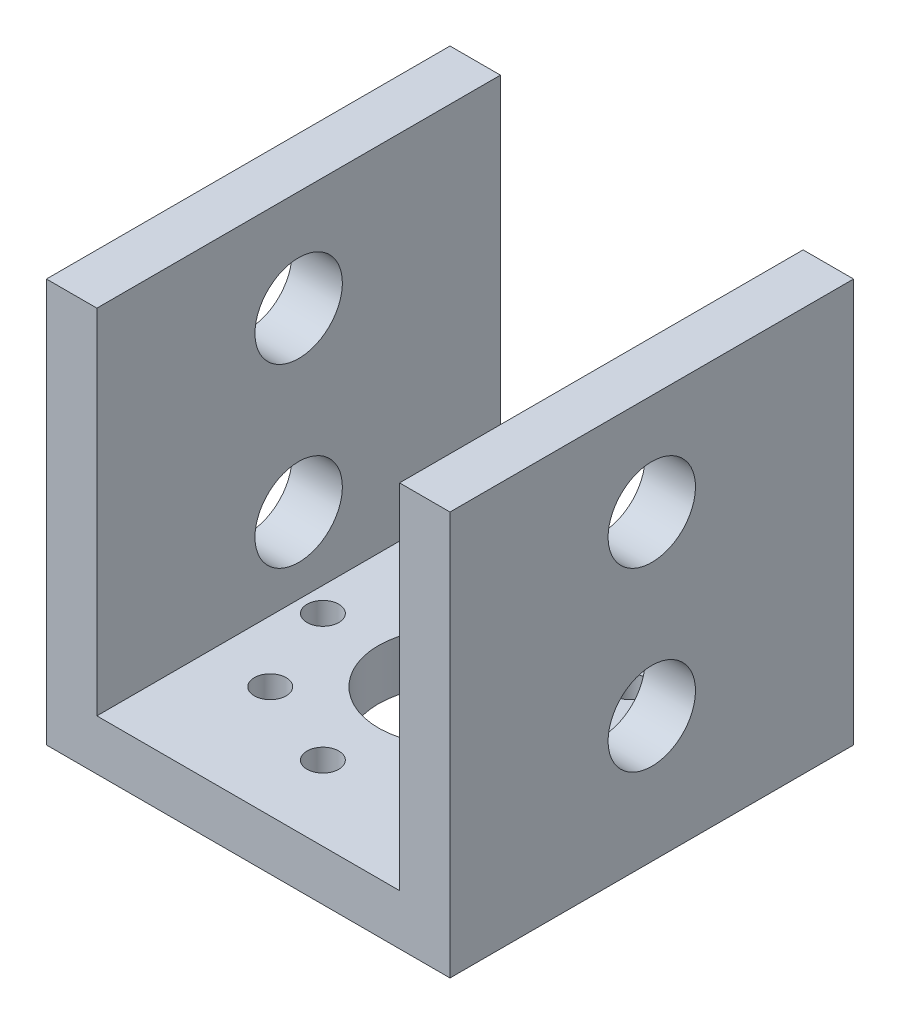
SolidWorks part; units mm, degrees
material "6063-T5"
ref_plane "Front Plane" through (0, 0, 0) normal (0, 0, 1) x (1, 0, 0)
ref_plane "Top Plane" through (0, 0, 0) normal (0, 1, 0) x (1, 0, 0)
ref_plane "Right Plane" through (0, 0, 0) normal (1, 0, 0) x (0, 0, -1)
sketch "Sketch1" plane through (0, 0, 0) normal (0, 0, 1) x (1, 0, 0)
  line L0 (-9.525, 0) -> (9.525, 0)
  line L1 (0, 0) -> (0, -3.175) construction
  line L2 (-12.7, -3.175) -> (12.7, -3.175)
  line L3 (12.7, -3.175) -> (12.7, 22.225)
  line L4 (-12.7, -3.175) -> (-12.7, 22.225)
  line L5 (-9.525, 0) -> (-9.525, 22.225)
  line L6 (-9.525, 22.225) -> (-12.7, 22.225)
  line L7 (9.525, 0) -> (9.525, 22.225)
  line L8 (9.525, 22.225) -> (12.7, 22.225)
  point P3 (0, 0)
  point P9 (0, -3.175)
  dimension "D1" = 19.05
  dimension "D2" = 3.175
  dimension "D3" = 25.4
  dimension "D4" = 25.4
extrude "Boss-Extrude1" add sketch "Sketch1" along normal blind 25.4
sketch "Sketch2" plane through (12.7, 0, 0) normal (1, 0, 0) x (0, 0, -1)
  line L0 (-25.4, 22.225) -> (0, 22.225) construction
  line L1 (-25.4, -3.175) -> (-25.4, 22.225) construction
  line L3 (-25.4, -3.175) -> (0, -3.175) construction
  circle A0 centre (-12.7, 15.875) radius 2.75
  circle A1 centre (-12.7, 4.7625) radius 2.75
  point P6 (-12.7, 22.225)
  dimension "D1" = 5.5
  dimension "D4" = 7.9375
  dimension "D2" = 6.35
  dimension "D3" = 12.7
extrude "Cut-Extrude1" cut sketch "Sketch2" against normal through all
sketch "Sketch3" plane through (0, 0, 0) normal (0, 1, 0) x (1, 0, 0)
  line L0 (-9.525, 0) -> (9.525, -25.4) construction
  circle A0 centre (0, -12.7) radius 4.5
  point P6 (0, -4.7)
  point P10 (5.6569, -7.0431)
  point P11 (8, -12.7)
  point P12 (5.6569, -18.3569)
  point P13 (0, -20.7)
  point P14 (-5.6569, -18.3569)
  point P15 (-8, -12.7)
  point P16 (-5.6569, -7.0431)
  point P17 (0, -12.7)
  dimension "D1" = 9
  dimension "D2" = 8
  dimension "D3" = 8
extrude "Cut-Extrude2" cut sketch "Sketch3" against normal through all
hole_wizard "Ø2.0mm Dowel Hole1" positions "Sketch4" profile "Sketch5" hole size "Ø2.0" standard "ISO" end condition through all
sketch "Sketch4" plane through (0, 0, 0) normal (0, 1, 0) x (1, 0, 0)
  point P0 (0, -4.7)
  point P3 (5.6569, -7.0431)
  point P6 (8, -12.7)
  point P9 (5.6569, -18.3569)
  point P12 (0, -20.7)
  point P15 (-5.6569, -18.3569)
  point P18 (-8, -12.7)
  point P21 (-5.6569, -7.0431)
sketch "Sketch5" plane through (0, 0, 4.7) normal (1, 0, 0) x (0, 0, 1)
  line L0 (0, 0) -> (0, 3.175)
  line L1 (0, 3.175) -> (1, 3.175)
  line L2 (1, 3.175) -> (1, 0)
  line L5 (1, 0) -> (0, 0)
  line L11 (0, -6.35) -> (0, 107.95) construction
  dimension "Thru Hole Dia." = 2
  dimension "Thru Hole Depth" = 3.175
